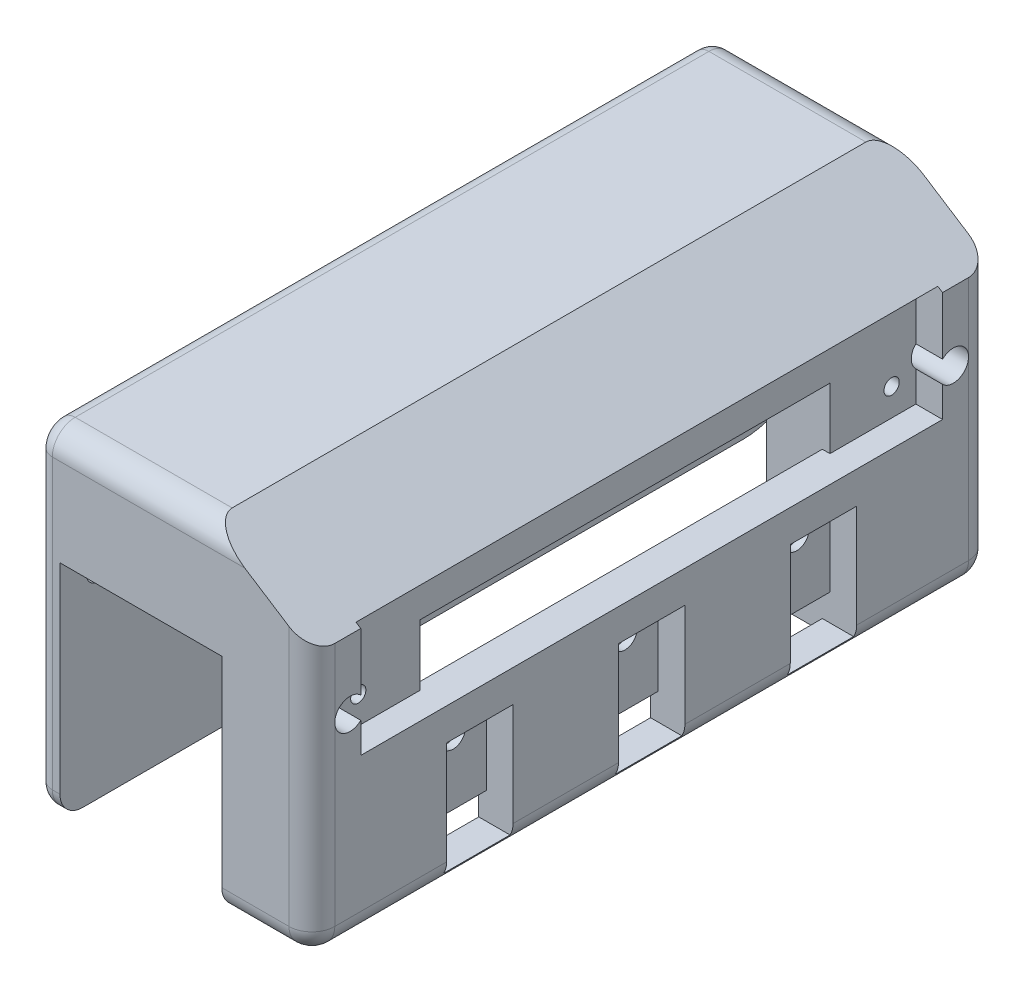
SolidWorks part; units mm, degrees
material "ABS"
ref_plane "Plano frontal" through (0, 0, 0) normal (0, 0, 1) x (1, 0, 0)
ref_plane "Plano superior" through (0, 0, 0) normal (0, 1, 0) x (1, 0, 0)
ref_plane "Plano direito" through (0, 0, 0) normal (1, 0, 0) x (0, 0, -1)
sketch "Esboço2" plane through (0, 0, 0) normal (1, 0, 0) x (0, 0, -1)
  line L1 (2.9016, -0.0625) -> (-35.0984, -0.0625) construction
  line L2 (2.9016, -0.0625) -> (-35.0984, -0.0625)
  line L6 (7.6893, -0.0625) -> (2.9016, -0.0625)
  line L8 (-39.8861, -0.0625) -> (-35.0984, -0.0625)
  line L9 (-60.5984, 9.4769) -> (-60.5984, 20.9769)
  line L10 (28.4016, 9.4769) -> (28.4016, 20.9769)
  line L11 (-57.5984, 23.9769) -> (25.4016, 23.9769)
  arc A0 (28.4016, 20.9769) -> (25.4016, 23.9769) centre (25.4016, 20.9769) ccw
  arc A1 (-60.5984, 20.9769) -> (-57.5984, 23.9769) centre (-57.5984, 20.9769) cw
  arc A2 (28.4016, 9.4769) -> (24.5016, 12.3387) centre (25.4016, 9.4769) ccw
  arc A3 (-48.8914, 5.5897) -> (-56.6984, 12.3387) centre (-60.5984, -0.0625) ccw
  arc A4 (-48.8914, 5.5897) -> (-39.8861, -0.0625) centre (-39.8861, 9.9375) ccw
  arc A5 (-60.5984, 9.4769) -> (-56.6984, 12.3387) centre (-57.5984, 9.4769) cw
  arc A6 (16.6946, 5.5897) -> (7.6893, -0.0625) centre (7.6893, 9.9375) cw
  arc A7 (16.6946, 5.5897) -> (24.5016, 12.3387) centre (28.4016, -0.0625) cw
  point P22 (28.4016, 12.9375)
  point P23 (-60.5984, 12.9375)
  dimension "D1" = 3
extrude "Ressalto-extrusão2" add sketch "Esboço2" along normal blind 30
sketch "Esboço3" plane through (0, 0, 0) normal (-1, 0, 0) x (0, 0, 1)
  line L0 (60.5984, 15.2269) -> (60.5984, 20.9769)
  line L1 (60.5984, 20.9769) -> (60.5984, 9.4769) construction
  line L2 (-28.4016, 15.2269) -> (-28.4016, 20.9769)
  line L3 (-28.4016, 9.4769) -> (-28.4016, 20.9769) construction
  line L4 (16.0984, 23.9769) -> (57.5984, 23.9769)
  line L5 (-25.4016, 23.9769) -> (57.5984, 23.9769) construction
  line L6 (16.0984, 23.9769) -> (-25.4016, 23.9769)
  line L7 (60.5984, 15.2269) -> (60.5984, -16.7731)
  line L8 (-28.4016, 15.2269) -> (-28.4016, -16.7731)
  line L9 (57.5984, -19.7731) -> (-25.4016, -19.7731)
  arc A0 (57.5984, 23.9769) -> (60.5984, 20.9769) centre (57.5984, 20.9769) cw
  arc A1 (-28.4016, 20.9769) -> (-25.4016, 23.9769) centre (-25.4016, 20.9769) cw
  arc A2 (-28.4016, -16.7731) -> (-25.4016, -19.7731) centre (-25.4016, -16.7731) ccw
  arc A3 (60.5984, -16.7731) -> (57.5984, -19.7731) centre (57.5984, -16.7731) cw
  dimension "D1" = 3
  dimension "D2" = 3
extrude "Ressalto-extrusão3" add sketch "Esboço3" along normal blind 3
sketch "Esboço4" plane through (30, 0, 0) normal (1, 0, 0) x (0, 0, -1)
  line L0 (-16.0984, 23.9769) -> (25.4016, 23.9769)
  line L1 (25.4016, 23.9769) -> (-57.5984, 23.9769) construction
  line L2 (-16.0984, 23.9769) -> (-57.5984, 23.9769)
  line L3 (28.4016, 15.2269) -> (28.4016, 20.9769)
  line L4 (28.4016, 9.4769) -> (28.4016, 20.9769) construction
  line L5 (-60.5984, 20.9769) -> (-60.5984, 15.2269)
  line L7 (28.4016, 15.2269) -> (28.4016, -16.7731)
  line L8 (28.4016, 9.4769) -> (28.4016, -16.7731) construction
  line L9 (-60.5984, 20.9769) -> (-60.5984, 9.4769) construction
  line L10 (-60.5984, 15.2269) -> (-60.5984, -16.7731)
  line L11 (25.4016, -19.7731) -> (-57.5984, -19.7731)
  arc A0 (25.4016, 23.9769) -> (28.4016, 20.9769) centre (25.4016, 20.9769) cw
  arc A1 (-60.5984, 20.9769) -> (-57.5984, 23.9769) centre (-57.5984, 20.9769) cw
  arc A2 (-60.5984, -16.7731) -> (-57.5984, -19.7731) centre (-57.5984, -16.7731) ccw
  arc A3 (28.4016, -16.7731) -> (25.4016, -19.7731) centre (25.4016, -16.7731) cw
  point P23 (28.4016, -19.7731)
  dimension "D1" = 3
extrude "Ressalto-extrusão4" add sketch "Esboço4" along normal blind 3 and the other way blind 8.8
sketch "Esboço10" plane through (0, 0, 0) normal (1, 0, 0) x (0, 0, -1)
  line L0 (-60.5984, -16.7731) -> (-60.5984, 9.4769) construction
  line L1 (28.4016, 9.4769) -> (28.4016, -16.7731) construction
  line L2 (-39.8861, -0.0625) -> (7.6893, -0.0625) construction
  circle A0 centre (-55.5984, 6.3387) radius 1.5
  circle A1 centre (23.4016, 6.3387) radius 1.5
  circle A2 centre (-16.0984, -8.5625) radius 1.5
  dimension "D1" = 3
  dimension "D2" = 3
  dimension "D3" = 3
  dimension "D4" = 5
  dimension "D5" = 6
  dimension "D6" = 5
  dimension "D7" = 6
  dimension "D8" = 8.5
  dimension "D9" = 44.5
extrude "Corte-extrusão3" cut sketch "Esboço10" against normal blind 10
sketch "Esboço12" plane through (0, 0, 0) normal (1, 0, 0) x (0, 0, -1)
  line L0 (28.4016, 9.4769) -> (28.4016, -16.7731) construction
  line L1 (-31.5984, -2.8625) -> (-25.5984, -2.8625)
  line L2 (-33.5984, -4.8625) -> (-33.5984, -14.7731)
  line L3 (-31.5984, -16.7731) -> (-25.5984, -16.7731)
  line L4 (-23.5984, -4.8625) -> (-23.5984, -14.7731)
  line L5 (-6.5984, -2.8625) -> (-0.5984, -2.8625)
  line L6 (-8.5984, -4.8625) -> (-8.5984, -14.7731)
  line L7 (-6.5984, -16.7731) -> (-0.5984, -16.7731)
  line L8 (1.4016, -4.8625) -> (1.4016, -14.7731)
  line L9 (-60.5984, -16.7731) -> (-60.5984, 9.4769) construction
  line L10 (25.4016, -19.7731) -> (-57.5984, -19.7731) construction
  line L11 (-39.8861, -0.0625) -> (7.6893, -0.0625) construction
  arc A0 (-0.5984, -2.8625) -> (1.4016, -4.8625) centre (-0.5984, -4.8625) cw
  arc A1 (-0.5984, -16.7731) -> (1.4016, -14.7731) centre (-0.5984, -14.7731) ccw
  arc A2 (-8.5984, -14.7731) -> (-6.5984, -16.7731) centre (-6.5984, -14.7731) ccw
  arc A3 (-6.5984, -2.8625) -> (-8.5984, -4.8625) centre (-6.5984, -4.8625) ccw
  arc A4 (-25.5984, -2.8625) -> (-23.5984, -4.8625) centre (-25.5984, -4.8625) cw
  arc A5 (-25.5984, -16.7731) -> (-23.5984, -14.7731) centre (-25.5984, -14.7731) ccw
  arc A6 (-31.5984, -2.8625) -> (-33.5984, -4.8625) centre (-31.5984, -4.8625) ccw
  arc A7 (-33.5984, -14.7731) -> (-31.5984, -16.7731) centre (-31.5984, -14.7731) ccw
  point P12 (-60.5984, -3.6481)
  point P21 (1.4016, -16.7731)
  point P24 (-8.5984, -16.7731)
  point P31 (-23.5984, -16.7731)
  point P36 (-33.5984, -16.7731)
  dimension "D9" = 2
  dimension "D1" = 52
  dimension "D2" = 52
  dimension "D3" = 3
  dimension "D4" = 3
  dimension "D5" = 2.8
  dimension "D6" = 2.8
  dimension "D7" = 10
  dimension "D8" = 10
extrude "Corte-extrusão4" cut sketch "Esboço12" against normal blind 10
fillet "Filete2" radius 2 8 edges at (-3, 23.0982, 59.7197) (-3, 2.1019, 60.5984) (-3, -18.8944, 59.7197) (-3, -19.7731, 16.0984) (-3, -18.8944, -27.5229) (-3, 2.1019, -28.4016) (-3, 23.0982, -27.5229) (-3, 23.9769, 16.0984)
sketch "Esboço13" plane through (-3, 0, 0) normal (-1, 0, 0) x (0, 0, 1)
  line L0 (57.5984, 21.9769) -> (-25.4016, 21.9769) construction
  line L2 (-26.4016, 20.9769) -> (-26.4016, -16.7731) construction
  circle A0 centre (27.4484, 3.9769) radius 1.5
  circle A1 centre (4.7484, 3.9769) radius 1.5
  point P10 (-26.4016, 2.1019)
  dimension "D1" = 22.7
  dimension "D2" = 3
  dimension "D3" = 3
  dimension "D4" = 18
  dimension "D5" = 31.15
extrude "Corte-extrusão5" cut sketch "Esboço13" against normal blind 16
sketch "Esboço14" plane through (33, 0, 0) normal (1, 0, 0) x (0, 0, -1)
  line L0 (25.4016, 23.9769) -> (-57.5984, 23.9769) construction
  line L1 (-54.1984, 15.7269) -> (22.0016, 15.7269)
  line L2 (-54.1984, 15.7269) -> (-54.1984, 0.9269)
  line L3 (-54.1984, 0.9269) -> (22.0016, 0.9269)
  line L4 (22.0016, 15.7269) -> (22.0016, 0.9269)
  line L5 (-54.1984, 15.7269) -> (22.0016, 0.9269) construction
  line L6 (-54.1984, 0.9269) -> (22.0016, 15.7269) construction
  line L8 (-57.5984, -19.7731) -> (25.4016, -19.7731) construction
  point P0 (-16.0984, 8.3269)
  point P9 (-16.0984, 23.9769)
  dimension "D1" = 76.2
  dimension "D2" = 14.8
  dimension "D3" = 20.7
extrude "Corte-extrusão6" cut sketch "Esboço14" against normal blind 3.5
sketch "Esboço15" plane through (29.5, 0, 0) normal (1, 0, 0) x (0, 0, -1)
  line L0 (0, 0) -> (74.93, 0)
  line L1 (0, 0) -> (0, 12.7)
  line L2 (74.93, 0) -> (74.93, 12.7)
  line L3 (0, 12.7) -> (74.93, 12.7)
  line L4 (45.847, 3.81) -> (46.863, 3.81)
  line L5 (46.355, 3.302) -> (46.355, 4.318)
  line L6 (43.307, 3.81) -> (44.323, 3.81)
  line L7 (43.815, 3.302) -> (43.815, 4.318)
  line L8 (40.767, 3.81) -> (41.783, 3.81)
  line L9 (41.275, 3.302) -> (41.275, 4.318)
  line L10 (28.067, 3.81) -> (29.083, 3.81)
  line L11 (28.575, 3.302) -> (28.575, 4.318)
  line L12 (30.607, 3.81) -> (31.623, 3.81)
  line L13 (31.115, 3.302) -> (31.115, 4.318)
  line L14 (33.147, 3.81) -> (34.163, 3.81)
  line L15 (33.655, 3.302) -> (33.655, 4.318)
  line L16 (35.687, 3.81) -> (36.703, 3.81)
  line L17 (36.195, 3.302) -> (36.195, 4.318)
  line L18 (38.227, 3.81) -> (39.243, 3.81)
  line L19 (38.735, 3.302) -> (38.735, 4.318)
  line L20 (45.847, 1.27) -> (46.863, 1.27)
  line L21 (46.355, 0.762) -> (46.355, 1.778)
  line L22 (43.307, 1.27) -> (44.323, 1.27)
  line L23 (43.815, 0.762) -> (43.815, 1.778)
  line L24 (40.767, 1.27) -> (41.783, 1.27)
  line L25 (41.275, 0.762) -> (41.275, 1.778)
  line L26 (28.067, 1.27) -> (29.083, 1.27)
  line L27 (28.575, 0.762) -> (28.575, 1.778)
  line L28 (30.607, 1.27) -> (31.623, 1.27)
  line L29 (31.115, 0.762) -> (31.115, 1.778)
  line L30 (33.147, 1.27) -> (34.163, 1.27)
  line L31 (33.655, 0.762) -> (33.655, 1.778)
  line L32 (35.687, 1.27) -> (36.703, 1.27)
  line L33 (36.195, 0.762) -> (36.195, 1.778)
  line L34 (38.227, 1.27) -> (39.243, 1.27)
  line L35 (38.735, 0.762) -> (38.735, 1.778)
  line L36 (25.527, 3.81) -> (26.543, 3.81)
  line L37 (26.035, 3.302) -> (26.035, 4.318)
  line L38 (22.987, 3.81) -> (24.003, 3.81)
  line L39 (23.495, 3.302) -> (23.495, 4.318)
  line L40 (20.447, 3.81) -> (21.463, 3.81)
  line L41 (20.955, 3.302) -> (20.955, 4.318)
  line L42 (1.4478, 2.54) -> (3.6322, 2.54)
  line L43 (2.54, 1.4478) -> (2.54, 3.6322)
  line L44 (71.2978, 2.54) -> (73.4822, 2.54)
  line L45 (72.39, 1.4478) -> (72.39, 3.6322)
  line L46 (52.2478, 2.54) -> (54.4322, 2.54)
  line L47 (53.34, 1.4478) -> (53.34, 3.6322)
  line L48 (57.3278, 2.54) -> (59.5122, 2.54)
  line L49 (58.42, 1.4478) -> (58.42, 3.6322)
sketch "Esboço16" plane through (29.5, 0, 0) normal (1, 0, 0) x (0, 0, -1)
  line L0 (-54.1984, 4.5169) -> (22.0016, 4.5169) construction
  line L1 (-54.1984, 15.7269) -> (-54.1984, 0.9269) construction
  line L2 (22.0016, 0.9269) -> (22.0016, 15.7269) construction
  line L5 (-16.0984, 15.7269) -> (-16.0984, 0.9269) construction
  line L6 (22.0016, 15.7269) -> (-54.1984, 15.7269) construction
  line L7 (-54.1984, 0.9269) -> (22.0016, 0.9269) construction
  circle A0 centre (-51.0234, 4.5169) radius 1
  circle A1 centre (18.8266, 4.5169) radius 1
  point P6 (-16.0984, 8.3269)
  dimension "D2" = 2
  dimension "D1" = 3.81
  dimension "D6" = 69.85
extrude "Corte-extrusão7" cut sketch "Esboço16" against normal up to surface (8.3 mm away) contours A0 | A1 up to face at (21.2, -1.5542, 16.0984)
sketch "Esboço17" plane through (33, 0, 0) normal (1, 0, 0) x (0, 0, -1)
  line L0 (6.4016, -19.7731) -> (6.4016, 23.9769) construction
  line L1 (-57.5984, -19.7731) -> (25.4016, -19.7731) construction
  line L2 (25.4016, 23.9769) -> (-57.5984, 23.9769) construction
  line L3 (-38.5984, -19.7731) -> (-38.5984, 23.9769) construction
  line L4 (-16.0984, -19.7731) -> (-16.0984, 23.9769) construction
  line L5 (22.0016, 15.7269) -> (-54.1984, 15.7269) construction
  line L6 (10.7516, -3.2731) -> (2.0516, -3.2731)
  line L7 (10.7516, -3.2731) -> (10.7516, -18.2731)
  line L8 (10.7516, -18.2731) -> (2.0516, -18.2731)
  line L9 (2.0516, -3.2731) -> (2.0516, -18.2731)
  line L10 (10.7516, -3.2731) -> (2.0516, -18.2731) construction
  line L11 (10.7516, -18.2731) -> (2.0516, -3.2731) construction
  line L12 (-11.7484, -3.2731) -> (-20.4484, -3.2731)
  line L13 (-11.7484, -3.2731) -> (-11.7484, -18.2731)
  line L14 (-11.7484, -18.2731) -> (-20.4484, -18.2731)
  line L15 (-20.4484, -3.2731) -> (-20.4484, -18.2731)
  line L16 (-11.7484, -3.2731) -> (-20.4484, -18.2731) construction
  line L17 (-11.7484, -18.2731) -> (-20.4484, -3.2731) construction
  line L18 (-34.2484, -3.2731) -> (-42.9484, -3.2731)
  line L19 (-34.2484, -3.2731) -> (-34.2484, -18.2731)
  line L20 (-34.2484, -18.2731) -> (-42.9484, -18.2731)
  line L21 (-42.9484, -3.2731) -> (-42.9484, -18.2731)
  line L22 (-34.2484, -3.2731) -> (-42.9484, -18.2731) construction
  line L23 (-34.2484, -18.2731) -> (-42.9484, -3.2731) construction
  point P10 (6.4016, -10.7731)
  point P15 (-16.0984, -10.7731)
  point P20 (-38.5984, -10.7731)
  dimension "D1" = 22.5
  dimension "D2" = 22.5
  dimension "D7" = 8.7
  dimension "D8" = 15
  dimension "D9" = 34
extrude "Corte-extrusão8" cut sketch "Esboço17" against normal blind 3.5
sketch "Esboço20" plane through (29.5, 0, 0) normal (1, 0, 0) x (0, 0, -1)
  line L0 (-38.5984, -3.2731) -> (-38.5984, -18.2731) construction
  line L1 (-34.2484, -3.2731) -> (-42.9484, -3.2731) construction
  line L2 (-42.9484, -18.2731) -> (-34.2484, -18.2731) construction
  line L3 (-16.0984, -3.2731) -> (-16.0984, -18.2731) construction
  line L4 (-11.7484, -3.2731) -> (-20.4484, -3.2731) construction
  line L5 (-20.4484, -18.2731) -> (-11.7484, -18.2731) construction
  line L6 (6.4016, -3.2731) -> (6.4016, -18.2731) construction
  line L7 (10.7516, -3.2731) -> (2.0516, -3.2731) construction
  line L8 (2.0516, -18.2731) -> (10.7516, -18.2731) construction
  circle A0 centre (-38.5984, -6.3131) radius 1.6
  circle A1 centre (-16.0984, -6.3131) radius 1.6
  circle A2 centre (6.4016, -6.3131) radius 1.6
  dimension "D1" = 3.2
  dimension "D2" = 3.04
extrude "Corte-extrusão9" cut sketch "Esboço20" against normal up to surface (8.3 mm away) up to face at (21.2, 4.5169, -17.8266)
sketch "Esboço21" plane through (29.5, 0, 0) normal (1, 0, 0) x (0, 0, -1)
  line L0 (-42.9484, -3.2731) -> (-42.9484, -18.2731) construction
  line L1 (-34.2484, -18.2731) -> (-42.9484, -18.2731)
  line L2 (-34.2484, -18.2731) -> (-34.2484, -14.7731)
  line L3 (-34.2484, -14.7731) -> (-42.9484, -14.7731)
  line L4 (-42.9484, -18.2731) -> (-42.9484, -14.7731)
  line L5 (-20.4484, -3.2731) -> (-20.4484, -18.2731) construction
  line L6 (-11.7484, -18.2731) -> (-20.4484, -18.2731)
  line L7 (-11.7484, -18.2731) -> (-11.7484, -14.7731)
  line L8 (-11.7484, -14.7731) -> (-20.4484, -14.7731)
  line L9 (-20.4484, -18.2731) -> (-20.4484, -14.7731)
  line L10 (2.0516, -3.2731) -> (2.0516, -18.2731) construction
  line L11 (10.7516, -18.2731) -> (2.0516, -18.2731)
  line L12 (10.7516, -18.2731) -> (10.7516, -14.7731)
  line L13 (10.7516, -14.7731) -> (2.0516, -14.7731)
  line L14 (2.0516, -18.2731) -> (2.0516, -14.7731)
  line L15 (-42.9484, -18.2731) -> (-34.2484, -18.2731) construction
  line L16 (-34.2484, -18.2731) -> (-34.2484, -3.2731) construction
  line L17 (-11.7484, -18.2731) -> (-11.7484, -3.2731) construction
  line L18 (10.7516, -18.2731) -> (10.7516, -3.2731) construction
  dimension "D1" = 3.5
extrude "Corte-extrusão10" cut sketch "Esboço21" against normal up to surface (8.3 mm away) up to face at (21.2, -6.3131, 17.6984)
sketch "Esboço22" plane through (29.5, 0, 0) normal (1, 0, 0) x (0, 0, -1)
  line L0 (-54.1984, 8.9269) -> (22.0016, 8.9269) construction
  line L1 (-54.1984, 15.7269) -> (-54.1984, 0.9269) construction
  line L2 (22.0016, 0.9269) -> (22.0016, 15.7269) construction
  line L6 (-54.1984, 0.9269) -> (22.0016, 0.9269) construction
  line L7 (-54.1984, 15.7269) -> (-54.1984, 0.9269) construction
  line L8 (-33.2384, 0.9269) -> (1.0416, 0.9269)
  line L9 (-33.2384, 0.9269) -> (-33.2384, 8.9269)
  line L10 (-33.2384, 8.9269) -> (1.0416, 8.9269)
  line L11 (1.0416, 0.9269) -> (1.0416, 8.9269)
  line L12 (22.0016, 0.9269) -> (22.0016, 15.7269) construction
  dimension "D1" = 8
  dimension "D2" = 20.96
  dimension "D3" = 20.96
extrude "Corte-extrusão11" cut sketch "Esboço22" against normal up to surface (8.3 mm away) up to face at (21.2, -16.5231, 16.0984)
sketch "Esboço23" plane through (0, -19.7731, 0) normal (0, -1, 0) x (1, 0, 0)
  line L0 (21.2, 57.5984) -> (21.2, -25.4016) construction
  line L1 (28.5, 42.9484) -> (21.2, 42.9484)
  line L2 (28.5, 42.9484) -> (28.5, -10.7516)
  line L3 (28.5, -10.7516) -> (21.2, -10.7516)
  line L4 (21.2, 42.9484) -> (21.2, -10.7516)
  line L5 (29.5, 42.9484) -> (33, 42.9484) construction
  line L6 (29.5, -10.7516) -> (33, -10.7516) construction
  line L7 (29.5, 42.9484) -> (29.5, 34.2484) construction
  dimension "D1" = 1
extrude "Corte-extrusão12" cut sketch "Esboço23" against normal up to surface (28.7 mm away) up to face at (25.35, 8.9269, 16.0984)
sketch "Esboço26" plane through (0, 0, 60.5984) normal (0, 0, 1) x (1, 0, 0)
  line L0 (33, 15.3269) -> (19.5556, 23.9769)
  line L1 (19.5556, 23.9769) -> (33, 23.9769)
  line L2 (33, 23.9769) -> (33, 15.3269)
extrude "Corte-extrusão15" cut sketch "Esboço26" against normal through all
sketch "Esboço27" plane through (21.2, 0, 0) normal (-1, 0, 0) x (0, 0, 1)
  circle A0 centre (-23.4016, 6.3387) radius 2
extrude "Corte-extrusão16" cut sketch "Esboço27" against normal blind 15.5 contours A0
sketch "Esboço29" plane through (21.2, 0, 0) normal (-1, 0, 0) x (0, 0, 1)
  circle A0 centre (55.5984, 6.3387) radius 2
  dimension "D1" = 4
extrude "Corte-extrusão17" cut sketch "Esboço29" against normal blind 15.5
fillet "Filete5" radius 3 5 edges at (33, -0.7231, 60.5984) (33, -18.8944, 59.7197) (33, -19.7731, 16.0984) (33, -18.8944, -27.5229) (33, -0.7231, -28.4016)
sketch "Esboço30" plane through (21.2, 0, 0) normal (1, 0, 0) x (0, 0, -1)
  line L0 (10.7516, 8.9269) -> (-42.9484, 8.9269) construction
  line L1 (10.7516, 8.9269) -> (-42.9484, 8.9269)
  line L2 (10.7516, 8.9269) -> (10.7516, 0.9269)
  line L3 (10.7516, 0.9269) -> (-42.9484, 0.9269)
  line L4 (-42.9484, 8.9269) -> (-42.9484, 0.9269)
  line L5 (-54.1984, 0.9269) -> (22.0016, 0.9269) construction
  line L6 (-42.9484, 8.9269) -> (-42.9484, 0.418) construction
  line L7 (10.7516, 8.9269) -> (10.7516, 0.418) construction
extrude "Corte-extrusão18" cut sketch "Esboço30" against normal up to surface (24.2 mm away) and the other way through all up to face at (-3, 3.9769, 6.2484)
